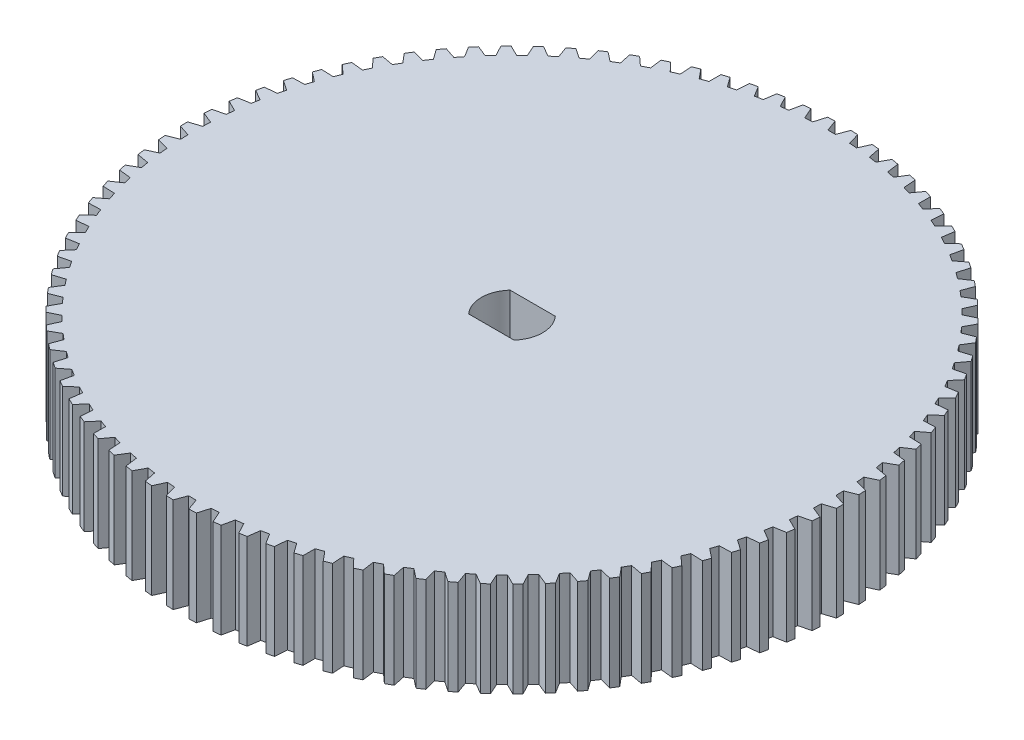
SolidWorks part; units mm, degrees
ref_plane "Front Plane" through (0, 0, 0) normal (0, 0, 1) x (1, 0, 0)
ref_plane "Top Plane" through (0, 0, 0) normal (0, 1, 0) x (1, 0, 0)
ref_plane "Right Plane" through (0, 0, 0) normal (1, 0, 0) x (0, 0, -1)
sketch "Sketch1" plane through (0, 0, 0) normal (0, 1, 0) x (1, 0, 0)
  line L0 (0, 0) -> (-28.8706, -16.4906) construction
  line L1 (-25.6111, -13.8265) -> (-24.5689, -13.6477)
  line L2 (-24.92, -15.0364) -> (-24.2366, -14.2295)
  line L3 (0, 0) -> (-37.4245, -18.039) construction
  line L4 (-26.5132, -12.0063) -> (-25.4611, -11.9006)
  line L5 (-25.9082, -13.2614) -> (-25.1702, -12.5042)
  line L6 (-27.2861, -10.1276) -> (-26.2292, -10.0956)
  line L7 (-26.7702, -11.4218) -> (-25.9811, -10.7179)
  line L8 (-27.9261, -8.1995) -> (-26.8695, -8.2413)
  line L9 (-27.5017, -9.5266) -> (-26.6654, -8.8795)
  line L10 (-28.4301, -6.2315) -> (-27.379, -6.3469)
  line L11 (-28.0993, -7.585) -> (-27.2199, -6.9978)
  line L12 (-28.7955, -4.2332) -> (-27.755, -4.4216)
  line L13 (-28.5599, -5.6064) -> (-27.6417, -5.082)
  line L14 (-29.0207, -2.2142) -> (-27.9958, -2.4747)
  line L15 (-28.8814, -3.6005) -> (-27.9289, -3.1414)
  line L16 (-29.1044, -0.1844) -> (-28.1003, -0.5158)
  line L17 (-29.0622, -1.5771) -> (-28.08, -1.1855)
  line L18 (-29.0464, 1.8463) -> (-28.0678, 1.4456)
  line L19 (-29.1015, 0.454) -> (-28.0943, 0.7761)
  line L20 (-28.8468, 3.8679) -> (-27.8986, 3.4)
  line L21 (-28.9989, 2.4829) -> (-27.9717, 2.734)
  line L22 (-28.5068, 5.8708) -> (-27.5935, 5.3378)
  line L23 (-28.7551, 4.4998) -> (-27.7129, 4.6786)
  line L24 (-28.0278, 7.845) -> (-27.1539, 7.2496)
  line L25 (-28.3711, 6.4946) -> (-27.319, 6.6003)
  line L26 (-27.4123, 9.781) -> (-26.582, 9.1261)
  line L27 (-27.849, 8.4579) -> (-26.792, 8.4899)
  line L28 (-26.6632, 11.6694) -> (-25.8807, 10.9582)
  line L29 (-27.1911, 10.3799) -> (-26.1345, 10.3381)
  line L30 (-25.7842, 13.5009) -> (-25.0532, 12.7368)
  line L31 (-26.4008, 12.2514) -> (-25.3497, 12.136)
  line L32 (-24.7797, 15.2666) -> (-24.1037, 14.4534)
  line L33 (-25.4819, 14.0632) -> (-24.4414, 13.8748)
  line L34 (-23.6544, 16.958) -> (-23.0368, 16.0996)
  line L35 (-24.4388, 15.8065) -> (-23.414, 15.5459)
  line L36 (-22.4138, 18.5667) -> (-21.8576, 17.6674)
  line L37 (-23.2767, 17.4727) -> (-22.2725, 17.1413)
  line L38 (-21.0641, 20.085) -> (-20.572, 19.149)
  line L39 (-22.0012, 19.0539) -> (-21.0226, 18.6532)
  line L40 (-19.6117, 21.5054) -> (-19.1861, 20.5374)
  line L41 (-20.6184, 20.5422) -> (-19.6702, 20.0742)
  line L42 (-18.0638, 22.8211) -> (-17.7067, 21.8257)
  line L43 (-19.1353, 21.9304) -> (-18.222, 21.3975)
  line L44 (-16.4279, 24.0255) -> (-16.1411, 23.0077)
  line L45 (-17.5589, 23.2118) -> (-16.685, 22.6164)
  line L46 (-14.7119, 25.113) -> (-14.4968, 24.0776)
  line L47 (-15.8969, 24.3801) -> (-15.0667, 23.7252)
  line L48 (-12.9243, 26.078) -> (-12.782, 25.0302)
  line L49 (-14.1575, 25.4296) -> (-13.375, 24.7184)
  line L50 (-11.0737, 26.9161) -> (-11.0048, 25.8609)
  line L51 (-12.3492, 26.3553) -> (-11.6181, 25.5912)
  line L52 (-9.1691, 27.623) -> (-9.174, 26.5655)
  line L53 (-10.4806, 27.1525) -> (-9.8047, 26.3393)
  line L54 (-7.2199, 28.1953) -> (-7.2986, 27.1408)
  line L55 (-8.561, 27.8174) -> (-7.9435, 26.9591)
  line L56 (-5.2355, 28.6302) -> (-5.3875, 27.5838)
  line L57 (-6.5997, 28.3469) -> (-6.0435, 27.4475)
  line L58 (-3.2256, 28.9257) -> (-3.4503, 27.8924)
  line L59 (-4.6063, 28.7382) -> (-4.1142, 27.8022)
  line L60 (-1.2, 29.0803) -> (-1.4962, 28.0651)
  line L61 (-2.5904, 28.9895) -> (-2.1648, 28.0215)
  line L62 (0.8314, 29.0931) -> (0.4652, 28.1012)
  line L63 (-0.5619, 29.0996) -> (-0.2048, 28.1043)
  line L64 (2.8588, 28.9643) -> (2.4243, 28.0002)
  line L65 (1.4694, 29.0679) -> (1.7561, 28.0501)
  line L66 (4.8723, 28.6943) -> (4.3716, 27.7629)
  line L67 (3.4935, 28.8946) -> (3.7085, 27.8592)
  line L68 (6.8621, 28.2845) -> (6.2976, 27.3904)
  line L69 (5.5006, 28.5805) -> (5.6429, 27.5327)
  line L70 (8.8184, 27.7369) -> (8.1929, 26.8843)
  line L71 (7.4808, 28.1272) -> (7.5497, 27.072)
  line L72 (10.7317, 27.0542) -> (10.0483, 26.2473)
  line L73 (9.4247, 27.5368) -> (9.4198, 26.4794)
  line L74 (12.5928, 26.2397) -> (11.8547, 25.4825)
  line L75 (11.3226, 26.8123) -> (11.2439, 25.7578)
  line L76 (14.3925, 25.2974) -> (13.6034, 24.5935)
  line L77 (13.1653, 25.9572) -> (13.0133, 24.9107)
  line L78 (16.1221, 24.2318) -> (15.2858, 23.5846)
  line L79 (14.9439, 24.9756) -> (14.7193, 23.9423)
  line L80 (17.7732, 23.0481) -> (16.8938, 22.4609)
  line L81 (16.6497, 23.8723) -> (16.3536, 22.8572)
  line L82 (19.3376, 21.7522) -> (18.4194, 21.2277)
  line L83 (18.2744, 22.6527) -> (17.9082, 21.6608)
  line L84 (20.8079, 20.3503) -> (19.8553, 19.8911)
  line L85 (19.8101, 21.3228) -> (19.3755, 20.3588)
  line L86 (22.1767, 18.8492) -> (21.1945, 18.4576)
  line L87 (21.2492, 19.889) -> (20.7485, 18.9576)
  line L88 (23.4376, 17.2563) -> (22.4304, 16.9342)
  line L89 (22.5849, 18.3582) -> (22.0204, 17.4641)
  line L90 (24.5842, 15.5794) -> (23.557, 15.3283)
  line L91 (23.8104, 16.7381) -> (23.185, 15.8855)
  line L92 (25.6111, 13.8265) -> (24.5689, 13.6477)
  line L93 (24.92, 15.0364) -> (24.2366, 14.2295)
  line L94 (26.5132, 12.0063) -> (25.4611, 11.9006)
  line L95 (25.9082, 13.2614) -> (25.1702, 12.5042)
  line L96 (27.2861, 10.1276) -> (26.2292, 10.0956)
  line L97 (26.7702, 11.4218) -> (25.9811, 10.7179)
  line L98 (27.9261, 8.1995) -> (26.8695, 8.2413)
  line L99 (27.5017, 9.5266) -> (26.6654, 8.8795)
  line L100 (28.4301, 6.2315) -> (27.379, 6.3469)
  line L101 (28.0993, 7.585) -> (27.2199, 6.9978)
  line L102 (28.7955, 4.2332) -> (27.755, 4.4216)
  line L103 (28.5599, 5.6064) -> (27.6417, 5.082)
  line L104 (29.0207, 2.2142) -> (27.9958, 2.4747)
  line L105 (28.8814, 3.6005) -> (27.9289, 3.1414)
  line L106 (29.1044, 0.1844) -> (28.1003, 0.5158)
  line L107 (29.0622, 1.5771) -> (28.08, 1.1855)
  line L108 (29.0464, -1.8463) -> (28.0678, -1.4456)
  line L109 (29.1015, -0.454) -> (28.0943, -0.7761)
  line L110 (28.8468, -3.8679) -> (27.8986, -3.4)
  line L111 (28.9989, -2.4829) -> (27.9717, -2.734)
  line L112 (28.5068, -5.8708) -> (27.5935, -5.3378)
  line L113 (28.7551, -4.4998) -> (27.7129, -4.6786)
  line L114 (28.0278, -7.845) -> (27.1539, -7.2496)
  line L115 (28.3711, -6.4946) -> (27.319, -6.6003)
  line L116 (27.4123, -9.781) -> (26.582, -9.1261)
  line L117 (27.849, -8.4579) -> (26.792, -8.4899)
  line L118 (26.6632, -11.6694) -> (25.8807, -10.9582)
  line L119 (27.1911, -10.3799) -> (26.1345, -10.3381)
  line L120 (25.7842, -13.5009) -> (25.0532, -12.7368)
  line L121 (26.4008, -12.2514) -> (25.3497, -12.136)
  line L122 (24.7797, -15.2666) -> (24.1037, -14.4534)
  line L123 (25.4819, -14.0632) -> (24.4414, -13.8748)
  line L124 (23.6544, -16.958) -> (23.0368, -16.0996)
  line L125 (24.4388, -15.8065) -> (23.414, -15.5459)
  line L126 (22.4138, -18.5667) -> (21.8576, -17.6674)
  line L127 (23.2767, -17.4727) -> (22.2725, -17.1413)
  line L128 (21.0641, -20.085) -> (20.572, -19.149)
  line L129 (22.0012, -19.0539) -> (21.0226, -18.6532)
  line L130 (19.6117, -21.5054) -> (19.1861, -20.5374)
  line L131 (20.6184, -20.5422) -> (19.6702, -20.0742)
  line L132 (18.0638, -22.8211) -> (17.7067, -21.8257)
  line L133 (19.1353, -21.9304) -> (18.222, -21.3975)
  line L134 (16.4279, -24.0255) -> (16.1411, -23.0077)
  line L135 (17.5589, -23.2118) -> (16.685, -22.6164)
  line L136 (14.7119, -25.113) -> (14.4968, -24.0776)
  line L137 (15.8969, -24.3801) -> (15.0667, -23.7252)
  line L138 (12.9243, -26.078) -> (12.782, -25.0302)
  line L139 (14.1575, -25.4296) -> (13.375, -24.7184)
  line L140 (11.0737, -26.9161) -> (11.0048, -25.8609)
  line L141 (12.3492, -26.3553) -> (11.6181, -25.5912)
  line L142 (9.1691, -27.623) -> (9.174, -26.5655)
  line L143 (10.4806, -27.1525) -> (9.8047, -26.3393)
  line L144 (7.2199, -28.1953) -> (7.2986, -27.1408)
  line L145 (8.561, -27.8174) -> (7.9435, -26.9591)
  line L146 (5.2355, -28.6302) -> (5.3875, -27.5838)
  line L147 (6.5997, -28.3469) -> (6.0435, -27.4475)
  line L148 (3.2256, -28.9257) -> (3.4503, -27.8924)
  line L149 (4.6063, -28.7382) -> (4.1142, -27.8022)
  line L150 (1.2, -29.0803) -> (1.4962, -28.0651)
  line L151 (2.5904, -28.9895) -> (2.1648, -28.0215)
  line L152 (-0.8314, -29.0931) -> (-0.4652, -28.1012)
  line L153 (0.5619, -29.0996) -> (0.2048, -28.1043)
  line L154 (-2.8588, -28.9643) -> (-2.4243, -28.0002)
  line L155 (-1.4694, -29.0679) -> (-1.7561, -28.0501)
  line L156 (-4.8723, -28.6943) -> (-4.3716, -27.7629)
  line L157 (-3.4935, -28.8946) -> (-3.7085, -27.8592)
  line L158 (-6.8621, -28.2845) -> (-6.2976, -27.3904)
  line L159 (-5.5006, -28.5805) -> (-5.6429, -27.5327)
  line L160 (-8.8184, -27.7369) -> (-8.1929, -26.8843)
  line L161 (-7.4808, -28.1272) -> (-7.5497, -27.072)
  line L162 (-10.7317, -27.0542) -> (-10.0483, -26.2473)
  line L163 (-9.4247, -27.5368) -> (-9.4198, -26.4794)
  line L164 (-12.5928, -26.2397) -> (-11.8547, -25.4825)
  line L165 (-11.3226, -26.8123) -> (-11.2439, -25.7578)
  line L166 (-14.3925, -25.2974) -> (-13.6034, -24.5935)
  line L167 (-13.1653, -25.9572) -> (-13.0133, -24.9107)
  line L168 (-16.1221, -24.2318) -> (-15.2858, -23.5846)
  line L169 (-14.9439, -24.9756) -> (-14.7193, -23.9423)
  line L170 (-17.7732, -23.0481) -> (-16.8938, -22.4609)
  line L171 (-16.6497, -23.8723) -> (-16.3536, -22.8572)
  line L172 (-19.3376, -21.7522) -> (-18.4194, -21.2277)
  line L173 (-18.2744, -22.6527) -> (-17.9082, -21.6608)
  line L174 (-20.8079, -20.3503) -> (-19.8553, -19.8911)
  line L175 (-19.8101, -21.3228) -> (-19.3755, -20.3588)
  line L176 (-22.1767, -18.8492) -> (-21.1945, -18.4576)
  line L177 (-21.2492, -19.889) -> (-20.7485, -18.9576)
  line L178 (-23.4376, -17.2563) -> (-22.4304, -16.9342)
  line L179 (-22.5849, -18.3582) -> (-22.0204, -17.4641)
  line L180 (-24.5842, -15.5794) -> (-23.557, -15.3283)
  line L181 (-23.8104, -16.7381) -> (-23.185, -15.8855)
  line L182 (-23.185, -15.8855) -> (0, 0)
  line L183 (0, 0) -> (-22.0204, -17.4641)
  circle A0 centre (0, 0) radius 29.105 construction
  circle A1 centre (0, 0) radius 28.105 construction
  arc A2 (-23.8104, -16.7381) -> (-23.4376, -17.2563) centre (0, 0) ccw
  arc A3 (-22.0204, -17.4641) -> (-22.4304, -16.9342) centre (0, 0) cw
  point P5 (-25.6111, -13.8265)
  point P6 (-24.92, -15.0364)
  point P15 (-26.5132, -12.0063)
  point P16 (-25.9082, -13.2614)
  point P21 (-27.2861, -10.1276)
  point P22 (-26.7702, -11.4218)
  point P27 (-27.9261, -8.1995)
  point P28 (-27.5017, -9.5266)
  point P33 (-28.4301, -6.2315)
  point P34 (-28.0993, -7.585)
  point P39 (-28.7955, -4.2332)
  point P40 (-28.5599, -5.6064)
  point P45 (-29.0207, -2.2142)
  point P46 (-28.8814, -3.6005)
  point P51 (-29.1044, -0.1844)
  point P52 (-29.0622, -1.5771)
  point P57 (-29.0464, 1.8463)
  point P58 (-29.1015, 0.454)
  point P63 (-28.8468, 3.8679)
  point P64 (-28.9989, 2.4829)
  point P69 (-28.5068, 5.8708)
  point P70 (-28.7551, 4.4998)
  point P75 (-28.0278, 7.845)
  point P76 (-28.3711, 6.4946)
  point P81 (-27.4123, 9.781)
  point P82 (-27.849, 8.4579)
  point P87 (-26.6632, 11.6694)
  point P88 (-27.1911, 10.3799)
  point P93 (-25.7842, 13.5009)
  point P94 (-26.4008, 12.2514)
  point P99 (-24.7797, 15.2666)
  point P100 (-25.4819, 14.0632)
  point P105 (-23.6544, 16.958)
  point P106 (-24.4388, 15.8065)
  point P111 (-22.4138, 18.5667)
  point P112 (-23.2767, 17.4727)
  point P117 (-21.0641, 20.085)
  point P118 (-22.0012, 19.0539)
  point P123 (-19.6117, 21.5054)
  point P124 (-20.6184, 20.5422)
  point P129 (-18.0638, 22.8211)
  point P130 (-19.1353, 21.9304)
  point P135 (-16.4279, 24.0255)
  point P136 (-17.5589, 23.2118)
  point P141 (-14.7119, 25.113)
  point P142 (-15.8969, 24.3801)
  point P147 (-12.9243, 26.078)
  point P148 (-14.1575, 25.4296)
  point P153 (-11.0737, 26.9161)
  point P154 (-12.3492, 26.3553)
  point P159 (-9.1691, 27.623)
  point P160 (-10.4806, 27.1525)
  point P165 (-7.2199, 28.1953)
  point P166 (-8.561, 27.8174)
  point P171 (-5.2355, 28.6302)
  point P172 (-6.5997, 28.3469)
  point P177 (-3.2256, 28.9257)
  point P178 (-4.6063, 28.7382)
  point P183 (-1.2, 29.0803)
  point P184 (-2.5904, 28.9895)
  point P189 (0.8314, 29.0931)
  point P190 (-0.5619, 29.0996)
  point P195 (2.8588, 28.9643)
  point P196 (1.4694, 29.0679)
  point P201 (4.8723, 28.6943)
  point P202 (3.4935, 28.8946)
  point P207 (6.8621, 28.2845)
  point P208 (5.5006, 28.5805)
  point P213 (8.8184, 27.7369)
  point P214 (7.4808, 28.1272)
  point P219 (10.7317, 27.0542)
  point P220 (9.4247, 27.5368)
  point P225 (12.5928, 26.2397)
  point P226 (11.3226, 26.8123)
  point P231 (14.3925, 25.2974)
  point P232 (13.1653, 25.9572)
  point P237 (16.1221, 24.2318)
  point P238 (14.9439, 24.9756)
  point P243 (17.7732, 23.0481)
  point P244 (16.6497, 23.8723)
  point P249 (19.3376, 21.7522)
  point P250 (18.2744, 22.6527)
  point P255 (20.8079, 20.3503)
  point P256 (19.8101, 21.3228)
  point P261 (22.1767, 18.8492)
  point P262 (21.2492, 19.889)
  point P267 (23.4376, 17.2563)
  point P268 (22.5849, 18.3582)
  point P273 (24.5842, 15.5794)
  point P274 (23.8104, 16.7381)
  point P279 (25.6111, 13.8265)
  point P280 (24.92, 15.0364)
  point P285 (26.5132, 12.0063)
  point P286 (25.9082, 13.2614)
  point P291 (27.2861, 10.1276)
  point P292 (26.7702, 11.4218)
  point P297 (27.9261, 8.1995)
  point P298 (27.5017, 9.5266)
  point P303 (28.4301, 6.2315)
  point P304 (28.0993, 7.585)
  point P309 (28.7955, 4.2332)
  point P310 (28.5599, 5.6064)
  point P315 (29.0207, 2.2142)
  point P316 (28.8814, 3.6005)
  point P321 (29.1044, 0.1844)
  point P322 (29.0622, 1.5771)
  point P327 (29.0464, -1.8463)
  point P328 (29.1015, -0.454)
  point P333 (28.8468, -3.8679)
  point P334 (28.9989, -2.4829)
  point P339 (28.5068, -5.8708)
  point P340 (28.7551, -4.4998)
  point P345 (28.0278, -7.845)
  point P346 (28.3711, -6.4946)
  point P351 (27.4123, -9.781)
  point P352 (27.849, -8.4579)
  point P357 (26.6632, -11.6694)
  point P358 (27.1911, -10.3799)
  point P363 (25.7842, -13.5009)
  point P364 (26.4008, -12.2514)
  point P369 (24.7797, -15.2666)
  point P370 (25.4819, -14.0632)
  point P375 (23.6544, -16.958)
  point P376 (24.4388, -15.8065)
  point P381 (22.4138, -18.5667)
  point P382 (23.2767, -17.4727)
  point P387 (21.0641, -20.085)
  point P388 (22.0012, -19.0539)
  point P393 (19.6117, -21.5054)
  point P394 (20.6184, -20.5422)
  point P399 (18.0638, -22.8211)
  point P400 (19.1353, -21.9304)
  point P405 (16.4279, -24.0255)
  point P406 (17.5589, -23.2118)
  point P411 (14.7119, -25.113)
  point P412 (15.8969, -24.3801)
  point P417 (12.9243, -26.078)
  point P418 (14.1575, -25.4296)
  point P423 (11.0737, -26.9161)
  point P424 (12.3492, -26.3553)
  point P429 (9.1691, -27.623)
  point P430 (10.4806, -27.1525)
  point P435 (7.2199, -28.1953)
  point P436 (8.561, -27.8174)
  point P441 (5.2355, -28.6302)
  point P442 (6.5997, -28.3469)
  point P447 (3.2256, -28.9257)
  point P448 (4.6063, -28.7382)
  point P453 (1.2, -29.0803)
  point P454 (2.5904, -28.9895)
  point P459 (-0.8314, -29.0931)
  point P460 (0.5619, -29.0996)
  point P465 (-2.8588, -28.9643)
  point P466 (-1.4694, -29.0679)
  point P471 (-4.8723, -28.6943)
  point P472 (-3.4935, -28.8946)
  point P477 (-6.8621, -28.2845)
  point P478 (-5.5006, -28.5805)
  point P483 (-8.8184, -27.7369)
  point P484 (-7.4808, -28.1272)
  point P489 (-10.7317, -27.0542)
  point P490 (-9.4247, -27.5368)
  point P495 (-12.5928, -26.2397)
  point P496 (-11.3226, -26.8123)
  point P501 (-14.3925, -25.2974)
  point P502 (-13.1653, -25.9572)
  point P507 (-16.1221, -24.2318)
  point P508 (-14.9439, -24.9756)
  point P513 (-17.7732, -23.0481)
  point P514 (-16.6497, -23.8723)
  point P519 (-19.3376, -21.7522)
  point P520 (-18.2744, -22.6527)
  point P525 (-20.8079, -20.3503)
  point P526 (-19.8101, -21.3228)
  point P531 (-22.1767, -18.8492)
  point P532 (-21.2492, -19.889)
  point P537 (-23.4376, -17.2563)
  point P538 (-22.5849, -18.3582)
  point P543 (-24.5842, -15.5794)
  point P544 (-23.8104, -16.7381)
  point P549 (0, 0)
  dimension "D1" = 58.21
  dimension "D2" = 1
  dimension "D3" = 40
  dimension "D4" = 4
  dimension "D5" = 0.67
  dimension "D6" = 90
extrude "Boss-Extrude1" add sketch "Sketch1" along normal blind 8.4 contours A3 L183 L182 L181 A2 L178 region at (-15.3484, 0, 11.3088)
pattern_circular "CirPattern1" count 90 over 360 about axis through (0, 8.4, 0) along (0, -1, 0) of "Boss-Extrude1" reverse direction yes
sketch "Sketch2" plane through (0, 8.4, 0) normal (0, 1, 0) x (1, 0, 0)
  line L1 (-2, 1.825) -> (2, 1.825)
  line L2 (-2, 1.825) -> (-2, -1.825)
  line L3 (-2, -1.825) -> (2, -1.825)
  line L4 (2, 1.825) -> (2, -1.825)
  line L5 (-2, 1.825) -> (2, -1.825) construction
  line L6 (-2, -1.825) -> (2, 1.825) construction
  circle A0 centre (0, 0) radius 2.7075
  point P0 (0, 0)
  dimension "D1" = 3.65
  dimension "D2" = 4
extrude "Cut-Extrude1" cut sketch "Sketch2" against normal blind 5 contours L4 L1 L2 L3 | L2 A0 | L4 A0 region at (0, 8.4, 0) region at (-2.2864, 8.4, 0) region at (2.2864, 8.4, 0)
sketch "Sketch3" plane through (0, 3.4, 0) normal (0, 1, 0) x (1, 0, 0)
  circle A0 centre (0, 0) radius 1.53
  dimension "D1" = 3.06
extrude "Cut-Extrude2" cut sketch "Sketch3" against normal through all
